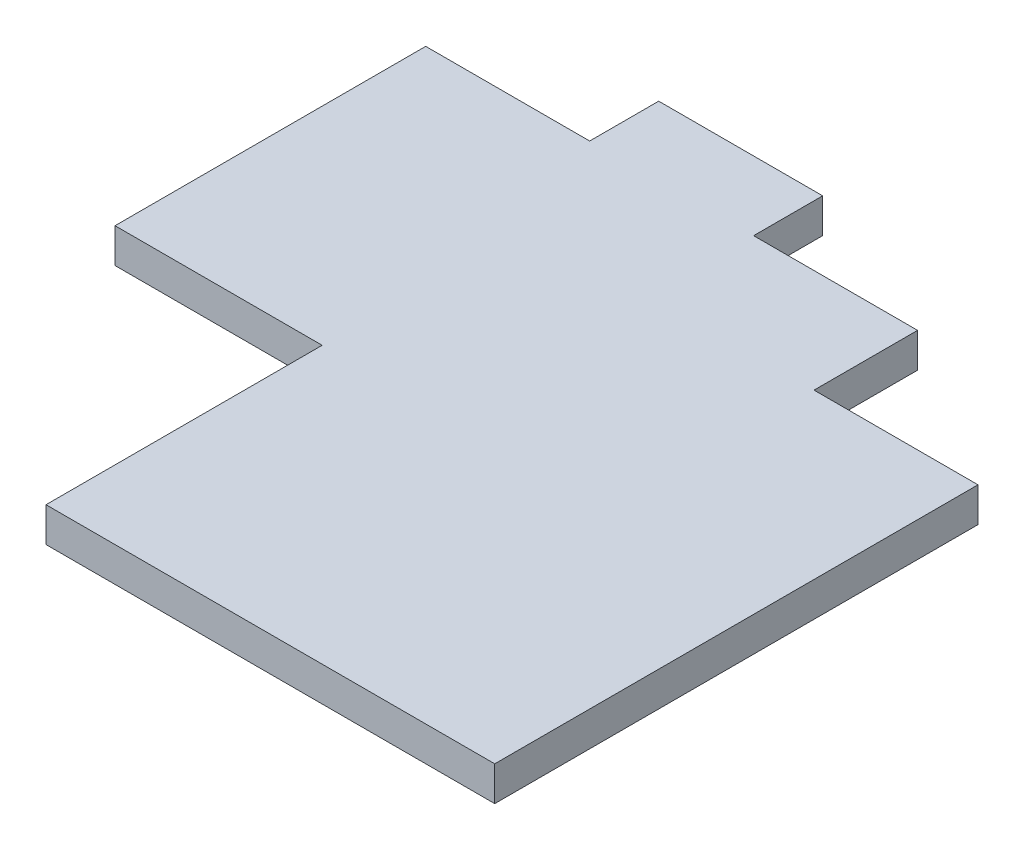
SolidWorks part; units mm, degrees
ref_plane "Front Plane" through (0, 0, 0) normal (0, 0, 1) x (1, 0, 0)
ref_plane "Top Plane" through (0, 0, 0) normal (0, 1, 0) x (1, 0, 0)
ref_plane "Right Plane" through (0, 0, 0) normal (1, 0, 0) x (0, 0, -1)
sketch "Sketch1" plane through (0, 0, 0) normal (0, 1, 0) x (1, 0, 0)
  line L1 (30, 0) -> (95, 0)
  line L2 (0, 40) -> (0, 85)
  line L3 (23.75, 95) -> (47.5, 95)
  line L4 (95, 0) -> (95, 70)
  line L7 (0, 85) -> (23.75, 85)
  line L8 (23.75, 95) -> (23.75, 85)
  line L10 (47.5, 95) -> (47.5, 85)
  line L14 (71.25, 85) -> (71.25, 70)
  line L15 (71.25, 70) -> (95, 70)
  line L17 (47.5, 85) -> (71.25, 85)
  line L21 (0, 40) -> (30, 40)
  line L22 (30, 0) -> (30, 40)
  dimension "D1" = 30
  dimension "D2" = 95
  dimension "D3" = 10
  dimension "D4" = 15
  dimension "D5" = 23.75
  dimension "D6" = 40
  dimension "D7" = 40
  dimension "D8" = 30
extrude "Boss-Extrude1" add sketch "Sketch1" along normal blind 5
